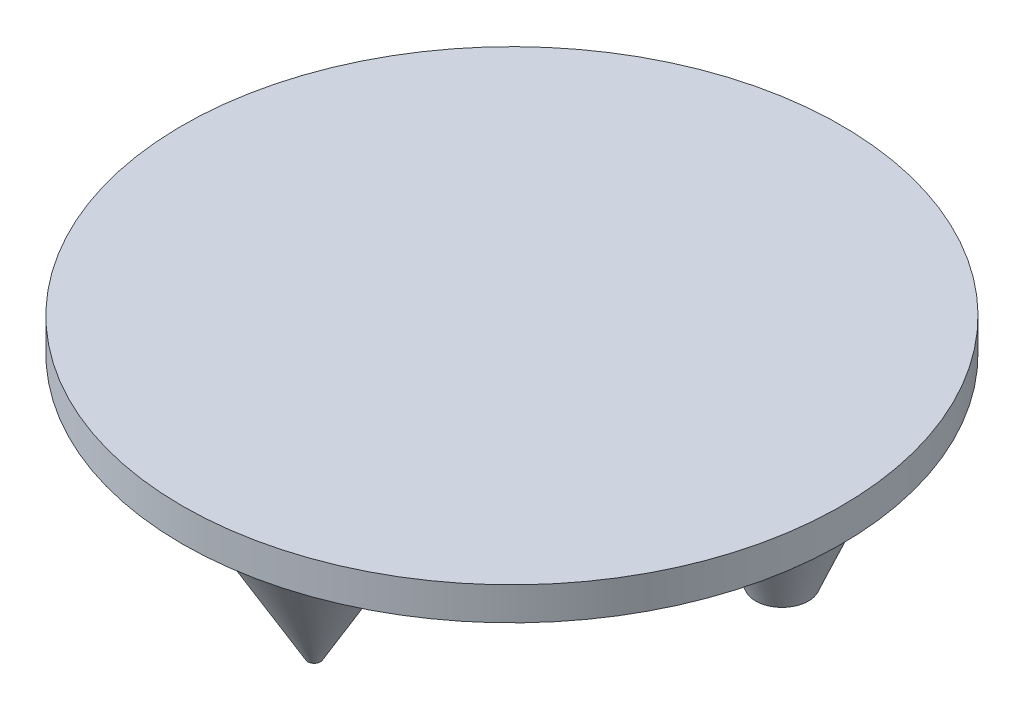
SolidWorks part; units mm, degrees
ref_plane "Front Plane" through (0, 0, 0) normal (0, 0, 1) x (1, 0, 0)
ref_plane "Top Plane" through (0, 0, 0) normal (0, 1, 0) x (1, 0, 0)
ref_plane "Right Plane" through (0, 0, 0) normal (1, 0, 0) x (0, 0, -1)
sketch "Sketch2" plane through (0, 0, 0) normal (0, 1, 0) x (1, 0, 0)
  circle A0 centre (0, 0) radius 12.7
  dimension "D1" = 25.4
extrude "Boss-Extrude1" add sketch "Sketch2" along normal blind 1.27
sketch "Sketch3" plane through (0, 0, 0) normal (0, -1, 0) x (1, 0, 0)
  circle A0 centre (0, 7.62) radius 3.175
  point P2 (0, 0)
  dimension "D1" = 6.35
  dimension "D2" = 7.62
extrude "Boss-Extrude2" add sketch "Sketch3" along normal blind 6.35
pattern_circular "CirPattern1" count 3 over 360 about axis through (0, 1.27, 0) along (0, -1, 0) of "Boss-Extrude2"
chamfer "Chamfer1" distance 5.08 angle 30 1 edges at (0, -6.35, 4.445) first distance on face at (0, -6.35, 4.445)
chamfer "Chamfer2" distance 5.08 angle 23 1 edges at (3.8495, -6.35, -2.2225) first distance on face at (3.8495, -6.35, -2.2225)
chamfer "Chamfer3" distance 5.08 angle 16 1 edges at (-3.8495, -6.35, -2.2225) first distance on face at (-3.8495, -6.35, -2.2225)
fillet "Fillet1" radius 2.54 3 edges at (6.5991, -1.27, -6.985) (0, -1.27, 4.445) (-6.5991, -1.27, -6.985)
